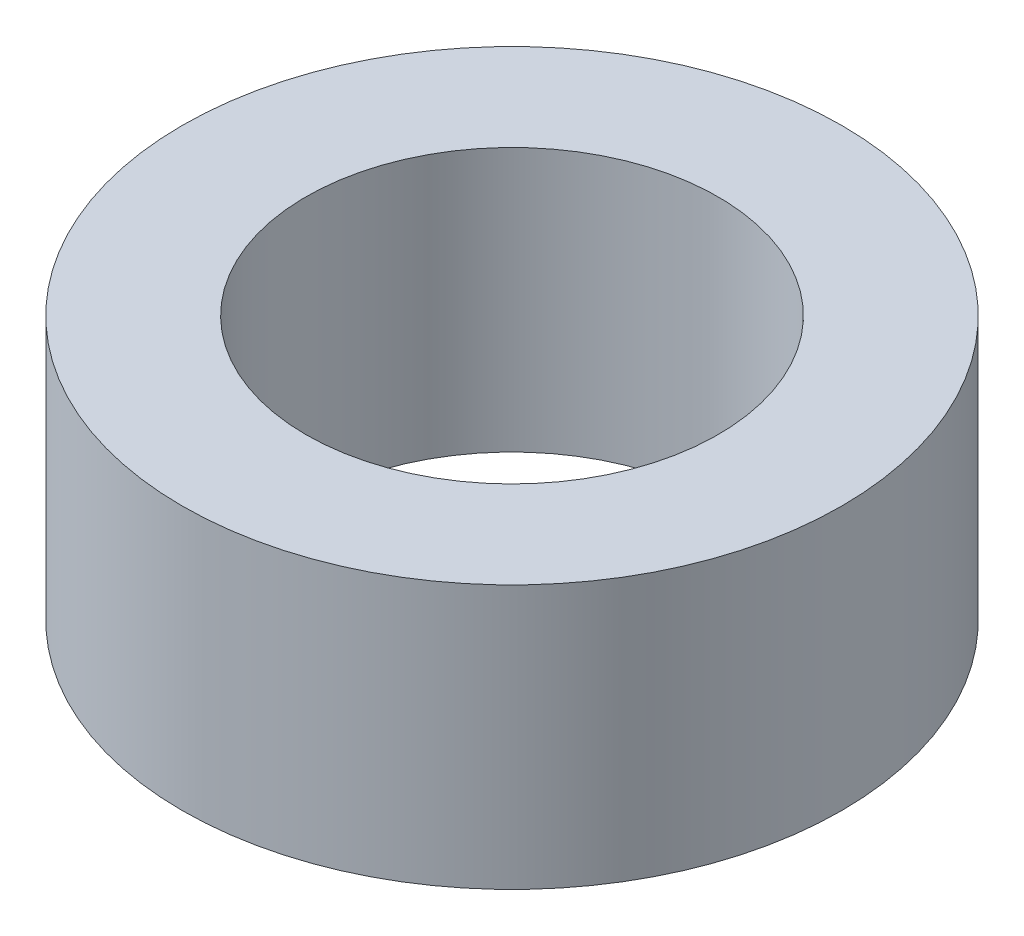
SolidWorks part; units mm, degrees
ref_plane "Front Plane" through (0, 0, 0) normal (0, 0, 1) x (1, 0, 0)
ref_plane "Top Plane" through (0, 0, 0) normal (0, 1, 0) x (1, 0, 0)
ref_plane "Right Plane" through (0, 0, 0) normal (1, 0, 0) x (0, 0, -1)
sketch "Sketch1" plane through (0, 0, 0) normal (0, 1, 0) x (1, 0, 0)
  circle A0 centre (0, 0) radius 20
  dimension "FLANGE_OD" = 40
extrude "Boss-Extrude1" add sketch "Sketch1" along normal blind 16
sketch "Sketch2" plane through (0, 0, 0) normal (0, 1, 0) x (1, 0, 0)
  circle A0 centre (0, 0) radius 12.5
  dimension "BORE_D" = 25
extrude "Cut-Extrude1" cut sketch "Sketch2" along normal through all
sketch "Sketch3" plane through (0, 16, 0) normal (0, 1, 0) x (1, 0, 0)
  circle A0 centre (0, 0) radius 8.0317 construction
  circle A1 centre (-8.0317, 0) radius 1.5
  dimension "BOLT_D" = 3
  dimension "BOLT_PCD" = 16.0634
extrude "Cut-Extrude2" cut sketch "Sketch3" against normal blind 9.8871 rebuild error yes
pattern_circular "CirPattern1" count 5 over 360 rebuild error yes
